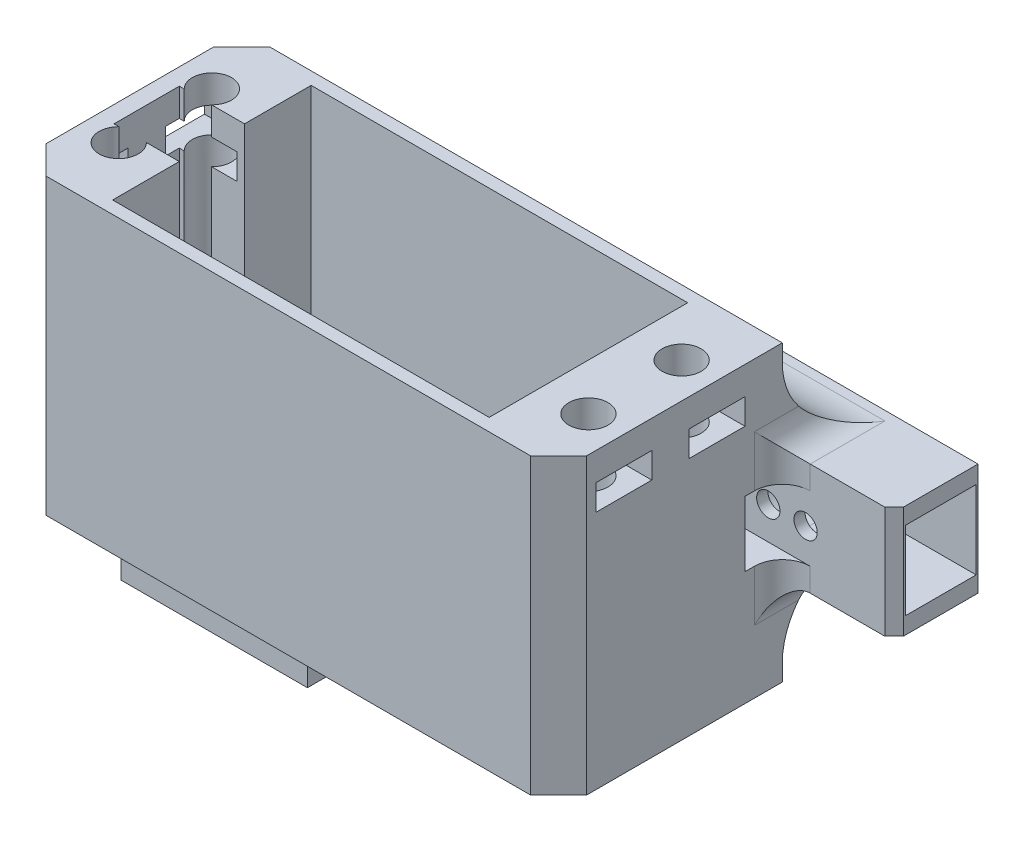
SolidWorks part; units mm, degrees
ref_plane "Front Plane" through (0, 0, 0) normal (0, 0, 1) x (1, 0, 0)
ref_plane "Top Plane" through (0, 0, 0) normal (0, 1, 0) x (1, 0, 0)
ref_plane "Right Plane" through (0, 0, 0) normal (1, 0, 0) x (0, 0, -1)
sketch "Sketch1" plane through (0, 0, 0) normal (0, 1, 0) x (1, 0, 0)
  line L0 (9.75, 1.0273) -> (50.15, 1.0273)
  line L1 (50.15, 1.0273) -> (50.15, -20.2727)
  line L2 (50.15, -20.2727) -> (9.75, -20.2727)
  line L4 (0.95, -21.6227) -> (58.95, -21.6227)
  line L5 (58.95, -21.6227) -> (58.95, 2.3773)
  line L6 (58.95, 2.3773) -> (0.95, 2.3773)
  line L8 (55.15, -4.6227) -> (55.15, -14.6227) construction
  line L9 (0.95, 2.3773) -> (0.95, -21.6227)
  line L10 (9.75, 1.0273) -> (9.75, -20.2727)
  line L11 (29.95, 1.0273) -> (29.95, -20.2727) construction
  circle A0 centre (55.15, -4.6227) radius 2.1
  circle A1 centre (55.15, -14.6227) radius 2.1
  circle A2 centre (4.75, -14.6227) radius 2.1
  circle A3 centre (4.75, -4.6227) radius 2.1
  point P13 (55.15, -9.6227)
  point P14 (50.15, -9.6227)
  point P20 (0.95, -9.6227)
  point P22 (29.95, 2.3773)
  dimension "D1" = 4.2
  dimension "D2" = 10
  dimension "D3" = 24
  dimension "D4" = 40.4
  dimension "D5" = 5
  dimension "D6" = 21.3
  dimension "D7" = 58
extrude "Boss-Extrude1" add sketch "Sketch1" along normal blind 28.35
sketch "Sketch11" plane through (0, 0, 0) normal (0, -1, 0) x (1, 0, 0)
  line L1 (0.95, 21.6227) -> (58.95, 21.6227)
  line L2 (0.95, 21.6227) -> (0.95, -2.3773)
  line L3 (0.95, -2.3773) -> (58.95, -2.3773)
  line L4 (58.95, 21.6227) -> (58.95, -2.3773)
extrude "Boss-Extrude5" add sketch "Sketch11" along normal blind 3.175
sketch "Sketch14" plane through (0, 0, -2.3773) normal (0, 0, -1) x (-1, 0, 0)
  line L7 (-58.95, 28.35) -> (-58.95, -3.175) construction
  line L8 (-46.95, 6.5875) -> (-70.95, 6.5875)
  line L9 (-46.95, 6.5875) -> (-46.95, 18.5875)
  line L10 (-46.95, 18.5875) -> (-70.95, 18.5875)
  line L11 (-70.95, 6.5875) -> (-70.95, 18.5875)
  line L12 (-46.95, 6.5875) -> (-70.95, 18.5875) construction
  line L13 (-46.95, 18.5875) -> (-70.95, 6.5875) construction
  point P0 (-58.95, 12.5875)
  point P5 (-58.95, 12.5875)
  dimension "D1" = 24
  dimension "D2" = 12
  dimension "D3" = 0
extrude "Boss-Extrude7" add sketch "Sketch14" along normal blind 10
ref_plane "Plane1" through (0, 0, -7.3773) normal (0, 0, 1) x (1, 0, 0)
sketch "Sketch16" plane through (0, 0, -7.3773) normal (0, 0, 1) x (1, 0, 0)
  line L0 (70.95, 18.5875) -> (70.95, 6.5875) construction
  line L1 (57.45, 8.3875) -> (70.95, 8.3875)
  line L3 (57.45, 16.7875) -> (70.95, 16.7875)
  line L4 (70.95, 8.3875) -> (70.95, 16.7875)
  line L5 (46.95, 6.5875) -> (46.95, 18.5875) construction
  arc A0 (57.45, 16.7875) -> (57.45, 8.3875) centre (57.45, 12.5875) ccw
  point P9 (46.95, 12.5875)
  point P10 (70.95, 12.5875)
  point P11 (0, 0)
  dimension "D2" = 4.2
  dimension "D1" = 13.5
extrude "Cut-Extrude1" cut sketch "Sketch16" against normal mid plane 7.6
sketch "Sketch18" plane through (0, 0, -12.3773) normal (0, 0, -1) x (-1, 0, 0)
  arc A0 (-60.2, 12.5875) -> (-62.7, 12.5875) centre (-61.45, 12.5875) ccw construction
  arc A1 (-62.7, 12.5875) -> (-60.2, 12.5875) centre (-61.45, 12.5875) ccw construction
  arc A2 (-56.2, 12.5875) -> (-58.7, 12.5875) centre (-57.45, 12.5875) ccw construction
  arc A3 (-58.7, 12.5875) -> (-56.2, 12.5875) centre (-57.45, 12.5875) ccw construction
  arc A4 (-60.2, 12.5875) -> (-62.7, 12.5875) centre (-61.45, 12.5875) ccw
  arc A5 (-62.7, 12.5875) -> (-60.2, 12.5875) centre (-61.45, 12.5875) ccw
  arc A6 (-56.2, 12.5875) -> (-58.7, 12.5875) centre (-57.45, 12.5875) ccw
  arc A7 (-58.7, 12.5875) -> (-56.2, 12.5875) centre (-57.45, 12.5875) ccw
extrude "Cut-Extrude2" cut sketch "Sketch18" against normal up to surface (10 mm away) up to face at (64.95, 12.5875, -2.3773)
fillet "Fillet1" radius 8 3 edges at (52.95, 6.5875, -2.3773) (46.95, 12.5875, -2.3773) (52.95, 18.5875, -2.3773)
chamfer "Chamfer2" distance 3 angle 45 3 edges at (0.95, 12.5875, -2.3773) (0.95, 12.5875, 21.6227) (58.95, 12.5875, 21.6227)
fillet "Fillet2" radius 3 2 edges at (58.95, 6.5875, -6.3773) (58.95, 18.5875, -6.3773)
fillet "Fillet3" radius 3 1 edges at (58.95, 12.5875, -2.3773)
chamfer "Chamfer3" distance 1 angle 45 5 edges at (70.95, 12.5875, -2.3773) (70.95, 12.5875, -12.3773) (58.95, 6.5875, -12.3773) (46.95, 12.5875, -12.3773) (58.95, 18.5875, -12.3773)
ref_plane "Plane2" through (0, 25.35, 0) normal (0, 1, 0) x (1, 0, 0)
sketch "Sketch19" plane through (0, 25.35, 0) normal (0, 1, 0) x (1, 0, 0)
  line L0 (0.95, -0.6227) -> (0.95, -18.6227) construction
  line L1 (0.95, -1.6227) -> (8.95, -1.6227)
  line L2 (0.95, -1.6227) -> (0.95, -7.6227)
  line L3 (0.95, -7.6227) -> (8.95, -7.6227)
  line L4 (8.95, -1.6227) -> (8.95, -7.6227)
  line L5 (-0.5892, -9.6227) -> (60.8708, -9.6227) construction
  line L6 (29.95, -22.0073) -> (29.95, 3.0189) construction
  line L7 (9.75, 1.0273) -> (9.75, -20.2727) construction
  line L8 (50.15, 1.0273) -> (9.75, 1.0273) construction
  line L9 (8.95, -17.6227) -> (8.95, -11.6227)
  line L10 (0.95, -11.6227) -> (8.95, -11.6227)
  line L11 (0.95, -17.6227) -> (0.95, -11.6227)
  line L12 (0.95, -17.6227) -> (8.95, -17.6227)
  line L37 (60.4892, -9.6227) -> (-0.9708, -9.6227) construction
  line L38 (58.95, -17.6227) -> (50.95, -17.6227)
  line L39 (58.95, -17.6227) -> (58.95, -11.6227)
  line L40 (58.95, -11.6227) -> (50.95, -11.6227)
  line L41 (50.95, -17.6227) -> (50.95, -11.6227)
  line L42 (50.95, -1.6227) -> (50.95, -7.6227)
  line L43 (58.95, -7.6227) -> (50.95, -7.6227)
  line L44 (58.95, -1.6227) -> (58.95, -7.6227)
  line L45 (58.95, -1.6227) -> (50.95, -1.6227)
  circle A0 centre (4.75, -4.6227) radius 2.1 construction
  circle A1 centre (4.75, -4.6227) radius 2.1 construction
  circle A2 centre (4.75, -14.6227) radius 2.1 construction
  circle A3 centre (4.75, -4.6227) radius 2.1 construction
  circle A4 centre (4.75, -14.6227) radius 2.1 construction
  circle A5 centre (4.75, -4.6227) radius 2.1 construction
  circle A6 centre (4.75, -14.6227) radius 2.1 construction
  circle A7 centre (4.75, -4.6227) radius 2.1 construction
  circle A8 centre (4.75, -14.6227) radius 2.1 construction
  circle A9 centre (55.15, -14.6227) radius 2.1 construction
  circle A10 centre (55.15, -4.6227) radius 2.1 construction
  circle A11 centre (55.15, -14.6227) radius 2.1 construction
  circle A12 centre (55.15, -4.6227) radius 2.1 construction
  circle A13 centre (55.15, -14.6227) radius 2.1 construction
  circle A14 centre (55.15, -4.6227) radius 2.1 construction
  circle A15 centre (55.15, -14.6227) radius 2.1 construction
  circle A16 centre (55.15, -4.6227) radius 2.1 construction
  point P11 (0.95, -4.6227)
  point P18 (9.75, -9.6227)
  point P21 (29.95, 1.0273)
  point P28 (0.95, -14.6227)
  point P55 (58.95, -14.6227)
  point P56 (58.95, -4.6227)
  dimension "D1" = 6
  dimension "D2" = 8
extrude "Cut-Extrude3" cut sketch "Sketch19" against normal blind 2.75
sketch "Sketch20" plane through (0, 0, 0) normal (0, 1, 0) x (1, 0, 0)
  line L0 (0.95, -0.6227) -> (0.95, -18.6227) construction
  line L1 (0.95, -13.8727) -> (9.75, -13.8727)
  line L2 (0.95, -13.8727) -> (0.95, -5.3727)
  line L3 (0.95, -5.3727) -> (9.75, -5.3727)
  line L4 (9.75, -13.8727) -> (9.75, -5.3727)
  line L5 (9.75, 1.0273) -> (9.75, -20.2727) construction
  point P6 (0.95, -9.6227)
  dimension "D1" = 8.5
extrude "Cut-Extrude4" cut sketch "Sketch20" along normal blind 4
sketch "Sketch21" plane through (0, -3.175, 0) normal (0, -1, 0) x (1, 0, 0)
  line L0 (0.95, 18.6227) -> (0.95, 0.6227) construction
  line L1 (30, -0.3773) -> (10, -0.3773)
  line L2 (30, -0.3773) -> (30, 19.6227)
  line L3 (30, 19.6227) -> (10, 19.6227)
  line L4 (10, -0.3773) -> (10, 19.6227)
  line L5 (30, -0.3773) -> (10, 19.6227) construction
  line L6 (30, 19.6227) -> (10, -0.3773) construction
  point P0 (20, 9.6227)
  point P7 (0.95, 9.6227)
  dimension "D1" = 19.05
  dimension "D2" = 20
  dimension "D3" = 20
extrude "Boss-Extrude8" add sketch "Sketch21" along normal blind 6
sketch "Sketch13" plane through (0, -9.175, 0) normal (0, -1, 0) x (1, 0, 0)
  line L0 (0.95, 18.6227) -> (0.95, 0.6227) construction
  circle A0 centre (20, 9.6227) radius 2.55
  point P2 (0.95, 9.6227)
  dimension "D2" = 5.1
  dimension "D1" = 19.05
extrude "Boss-Extrude6" add sketch "Sketch13" along normal blind 5
fillet "Fillet4" radius 1 4 edges at (20, -3.175, 19.6227) (30, -3.175, 9.6227) (20, -3.175, -0.3773) (10, -3.175, 9.6227)
chamfer "Chamfer4" distance 2 angle 45 4 edges at (20, -9.175, 19.6227) (30, -9.175, 9.6227) (20, -9.175, -0.3773) (10, -9.175, 9.6227)
fillet "Fillet5" radius 1 1 edges at (20, -14.175, 7.0727)
sketch "Sketch22" plane through (0, 28.35, 0) normal (0, 1, 0) x (1, 0, 0)
  line L0 (9.75, 1.0273) -> (9.75, -20.2727) construction
  line L2 (9.75, -6.1227) -> (2.75, -6.1227)
  line L3 (9.75, -6.1227) -> (9.75, -13.1227)
  line L4 (9.75, -13.1227) -> (2.75, -13.1227)
  line L5 (2.75, -6.1227) -> (2.75, -13.1227)
  point P0 (9.75, -9.6227)
  dimension "D1" = 7
  dimension "D2" = 7
extrude "Cut-Extrude5" cut sketch "Sketch22" against normal up to surface (28.35 mm away) up to face at (13.35, 0, 9.6227)
sketch "Sketch23" plane through (0, 0, -12.3773) normal (0, 0, -1) x (-1, 0, 0)
  line L14 (-69.95, 17.5875) -> (-69.95, 7.5875) construction
  line L15 (-64.6254, 16.0875) -> (-52.6254, 16.0875)
  line L16 (-64.6254, 16.0875) -> (-64.6254, 9.0875)
  line L17 (-64.6254, 9.0875) -> (-52.6254, 9.0875)
  line L18 (-52.6254, 16.0875) -> (-52.6254, 9.0875)
  point P0 (0, 0)
  point P4 (-69.95, 12.5875)
  point P5 (-64.6254, 12.5875)
  point P6 (0, 0)
  dimension "D1" = 7
  dimension "D2" = 12
  dimension "D4" = 5.3246
extrude "Cut-Extrude6" cut sketch "Sketch23" against normal blind 4 from surface starting at face at (64.7417, 12.5875, -2.3773)
